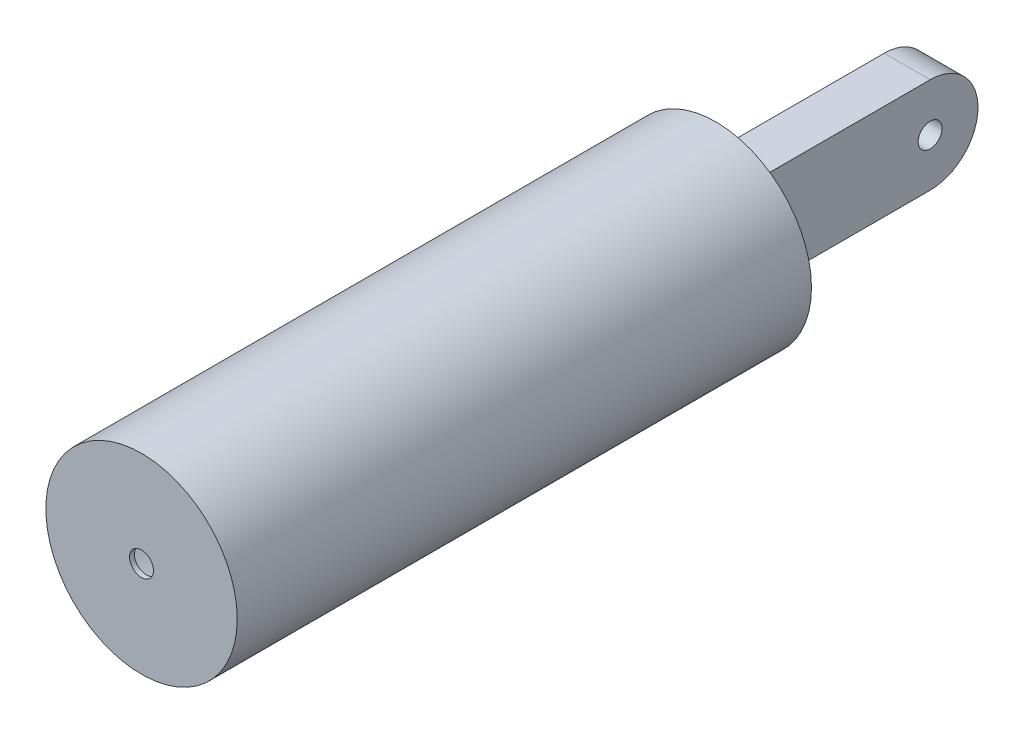
SolidWorks part; units mm, degrees
ref_plane "Front Plane" through (0, 0, 0) normal (0, 0, 1) x (1, 0, 0)
ref_plane "Top Plane" through (0, 0, 0) normal (0, 1, 0) x (1, 0, 0)
ref_plane "Right Plane" through (0, 0, 0) normal (1, 0, 0) x (0, 0, -1)
sketch "Sketch1" plane through (0, 0, 0) normal (0, 0, 1) x (1, 0, 0)
  circle A0 centre (0, 0) radius 10
  dimension "D1" = 20
extrude "Boss-Extrude1" add sketch "Sketch1" along normal mid plane 60
sketch "Sketch3" plane through (0, 0, 0) normal (0, 0, 1) x (1, 0, 0)
  circle A0 centre (0, 0) radius 9.75
  dimension "D1" = 19.5
extrude "Cut-Extrude1" cut sketch "Sketch3" against normal mid plane 59
sketch "Sketch4" plane through (0, 0, 30) normal (0, 0, 1) x (1, 0, 0)
  circle A0 centre (0, 0) radius 1.25
  dimension "D1" = 2.5
extrude "Cut-Extrude2" cut sketch "Sketch4" against normal blind 1
sketch "Sketch5" plane through (0, 0, 0) normal (1, 0, 0) x (0, 0, -1)
  line L0 (30, 5) -> (30, -5)
  line L1 (30, -10) -> (30, 10) construction
  line L2 (30, 5) -> (50, 5)
  line L4 (50, -5) -> (30, -5)
  arc A0 (50, -5) -> (50, 5) centre (50, 0) ccw
  point P4 (30, 0)
  dimension "D2" = 20
  dimension "D3" = 5
  dimension "D1" = 10
extrude "Boss-Extrude2" add sketch "Sketch5" along normal mid plane 4.8
sketch "Sketch6" plane through (2.4, 0, 0) normal (1, 0, 0) x (0, 0, -1)
  circle A0 centre (50, 0) radius 1.25
  arc A1 (50, -5) -> (50, 5) centre (50, 0) ccw construction
  dimension "D1" = 2.5
extrude "Cut-Extrude3" cut sketch "Sketch6" against normal blind 10
sketch "Sketch7" [suppressed] plane through (2.4, 0, 0) normal (1, 0, 0) x (0, 0, -1)
  circle A0 centre (40, 0) radius 1.25
  arc A1 (40, -5) -> (40, 5) centre (40, 0) ccw construction
  dimension "D1" = 2.5
extrude "Cut-Extrude4" [suppressed] cut sketch "Sketch7" against normal blind 10
ref_axis "Axis1" through (-2.4, 0, -50) along (1, 0, 0)
ref_point "Point1"
ref_axis "Axis2" [suppressed] through (-2.4, 0, -40) along (1, 0, 0)
ref_point "Point2" [suppressed]
